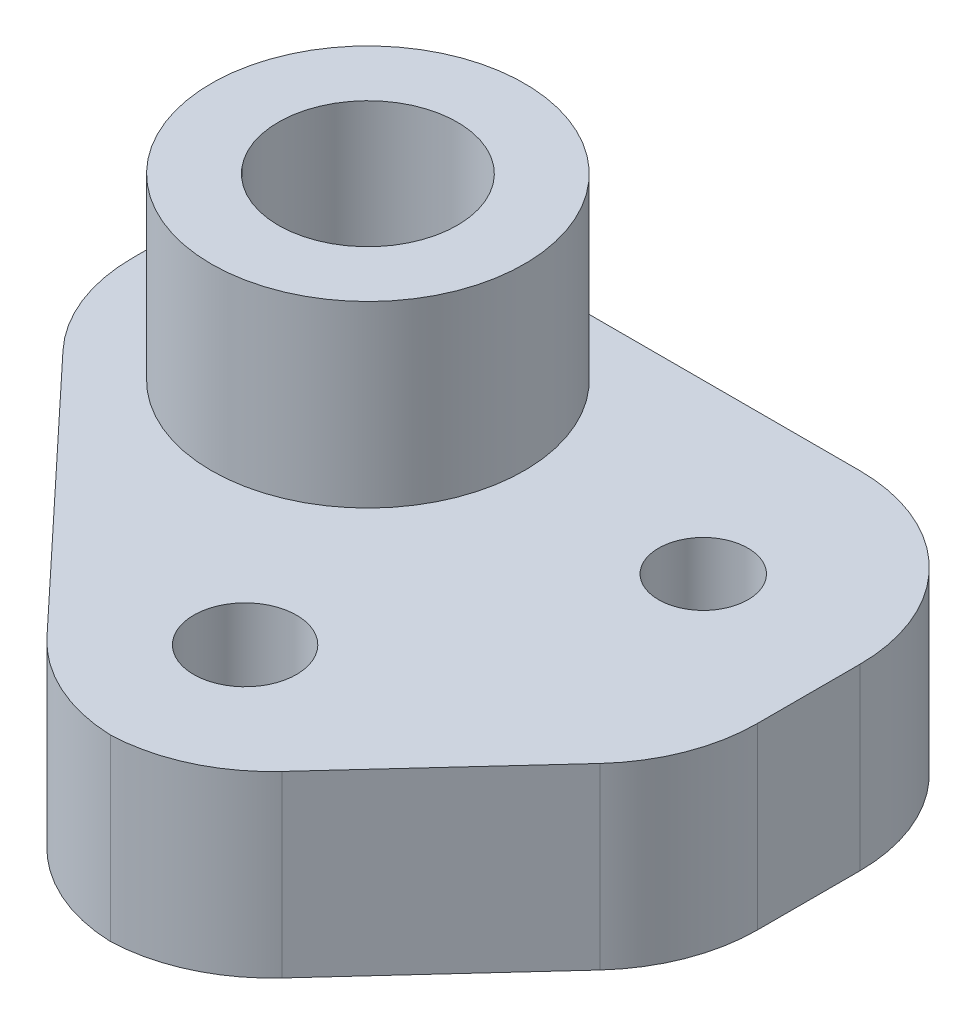
SolidWorks part; units mm, degrees
ref_plane "Plan de face" through (0, 0, 0) normal (0, 0, 1) x (1, 0, 0)
ref_plane "Plan de dessus" through (0, 0, 0) normal (0, 1, 0) x (1, 0, 0)
ref_plane "Plan de droite" through (0, 0, 0) normal (1, 0, 0) x (0, 0, -1)
sketch "Esquisse1" plane through (0, 0, 0) normal (0, 1, 0) x (1, 0, 0)
  line L0 (0, 0) -> (0, -7.5) construction
  line L1 (0, 0) -> (0, 7.5) construction
  line L2 (0, -7.5) -> (22, -7.5)
  line L3 (0, 7.5) -> (22, 7.5)
  line L4 (22, 7.5) -> (22, -7.5)
  line L5 (0, -7.5) -> (-10, -7.5)
  line L6 (-10, -7.5) -> (-10, 7.5)
  line L7 (-10, 7.5) -> (0, 7.5)
  line L8 (0, -7.5) -> (5, -7.5) construction
  line L9 (5, -19.5) -> (11, -19.5)
  line L10 (-10, -7.5) -> (14, -7.5) construction
  line L11 (11, -19.5) -> (22, -7.5)
  line L12 (-10, -7.5) -> (-10, -3.5) construction
  line L13 (-10, -3.5) -> (5, -19.5)
  line L14 (5, -7.5) -> (5, -19.5) construction
  dimension "D1" = 7.5
  dimension "D2" = 7.5
  dimension "D3" = 22
  dimension "D4" = 10
  dimension "D5" = 24
  dimension "D6" = 5
extrude "Boss.-Extru.1" add sketch "Esquisse1" along normal blind 8 contours L2 L5 | L7 L6 L5 L2 L4 L3 region at (6.2341, 0, -0.0979) region at (7.924, 0, 12.2007)
fillet "Congé1" radius 7.5 2 edges at (-10, 4, -7.5) (22, 4, -7.5)
sketch "Esquisse2" plane through (0, 8, 0) normal (0, 1, 0) x (1, 0, 0)
  line L0 (0, 0) -> (-15, 0) construction
  line L1 (0, 0) -> (15, 0) construction
  line L2 (0, 0) -> (7.5, -12.9904) construction
  circle A1 centre (15, 0) radius 2
  circle A2 centre (7.5, -12.9904) radius 2.3
  dimension "D1" = 15
  dimension "D3" = 60
  dimension "D2" = 15
extrude "Enlèv. mat.-Extru.1" cut sketch "Esquisse2" against normal up to next
sketch "Esquisse3" plane through (0, 8, 0) normal (0, 1, 0) x (1, 0, 0)
  circle A0 centre (0, 0) radius 7
  circle A1 centre (0, 0) radius 4
extrude "Boss.-Extru.2" add sketch "Esquisse3" along normal blind 8
fillet "Congé2" radius 7.5 4 edges at (22, 4, 7.5) (11, 4, 19.5) (5, 4, 19.5) (-10, 4, 3.5)
